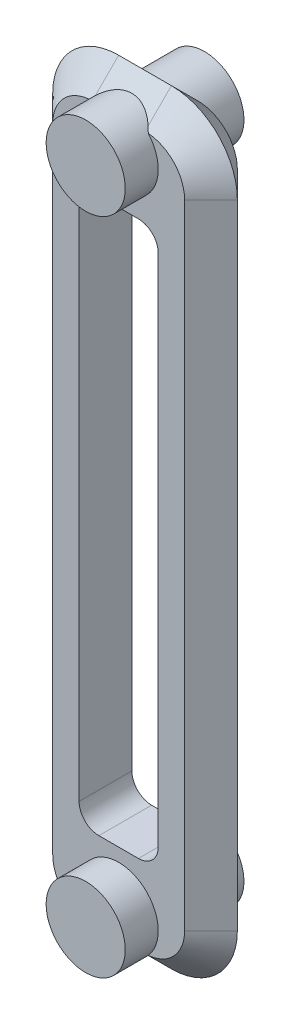
SolidWorks part; units mm, degrees
material "AISI 4340 Сталь, отожженная"
ref_plane "Спереди" through (0, 0, 0) normal (0, 0, 1) x (1, 0, 0)
ref_plane "Сверху" through (0, 0, 0) normal (0, 1, 0) x (1, 0, 0)
ref_plane "Справа" through (0, 0, 0) normal (1, 0, 0) x (0, 0, -1)
sketch "Эскиз1" plane through (0, 0, 0) normal (0, 0, 1) x (1, 0, 0)
  line L5 (0, 81.2166) -> (0, 71.2166)
  line L6 (0, -498.7834) -> (0, -488.7834)
  line L7 (70, 81.2166) -> (70, -498.7834)
  line L8 (-70, -498.7834) -> (-70, 81.2166)
  line L12 (70, 81.2166) -> (-70, 81.2166)
  line L14 (70, -498.7834) -> (-70, -498.7834)
  line L21 (0, 11.2166) -> (0, 1.2166)
  line L22 (0, 1.2166) -> (-30, 1.2166)
  line L23 (0, -428.7834) -> (0, -418.7834)
  line L24 (0, -418.7834) -> (-30, -418.7834)
  line L25 (-30, -418.7834) -> (-30, 1.2166)
  line L26 (0, 1.2166) -> (30, 1.2166)
  line L27 (30, 1.2166) -> (30, -418.7834)
  line L28 (30, -418.7834) -> (0, -418.7834)
  circle A0 centre (0, 41.2166) radius 30
  circle A1 centre (0, -458.7834) radius 30
extrude "Бобышка-Вытянуть1" add sketch "Эскиз1" along normal blind 20 and the other way blind 20 contours A0 | A0 | A0 | A0 | A1 | A1 | A1 | A1 | L8 L12 L7 L14 region at (0, 41.2166, 0) region at (0, -458.7834, 0)
sketch "Эскиз3" plane through (0, 0, -20) normal (0, 0, -1) x (-1, 0, 0)
  circle A0 centre (0, 41.2166) radius 30
  circle A1 centre (0, -458.7834) radius 30
extrude "Бобышка-Вытянуть2" add sketch "Эскиз3" along normal blind 25 and the other way blind 65
sketch "Эскиз4" plane through (0, 0, -20) normal (0, 0, -1) x (-1, 0, 0)
  line L1 (0, 11.2166) -> (0, 1.2166)
  line L3 (0, 1.2166) -> (30, 1.2166)
  line L4 (30, 1.2166) -> (30, -418.7834)
  line L5 (30, -418.7834) -> (0, -418.7834)
  line L6 (0, -418.7834) -> (-30, -418.7834)
  line L7 (-30, -418.7834) -> (-30, 1.2166)
  line L8 (-30, 1.2166) -> (0, 1.2166)
  circle A0 centre (0, 41.2166) radius 30 construction
extrude "Вырез-Вытянуть1" cut sketch "Эскиз4" against normal blind 40 contours L8 L7 L6 L5 L4 L3 region at (0, -208.7834, -20)
fillet "Скругление1" radius 50 4 edges at (70, -498.7834, 0) (-70, -498.7834, 0) (70, 81.2166, 0) (-70, 81.2166, 0)
fillet "Скругление2" radius 15 4 edges at (-30, -418.7834, 0) (30, -418.7834, 0) (30, 1.2166, 0) (-30, 1.2166, 0)
chamfer "Фаска1" distance 20 angle 45 16 edges at (0, -498.7834, -20) (-55.3553, -484.1387, -20) (55.3553, -484.1387, -20) (-70, -208.7834, -20) (70, -208.7834, -20) (-55.3553, 66.5719, -20) (55.3553, 66.5719, -20) (0, 81.2166, -20) (0, -498.7834, 20) (55.3553, -484.1387, 20) (-55.3553, -484.1387, 20) (70, -208.7834, 20) (-70, -208.7834, 20) (55.3553, 66.5719, 20) (-55.3553, 66.5719, 20) (0, 81.2166, 20)
